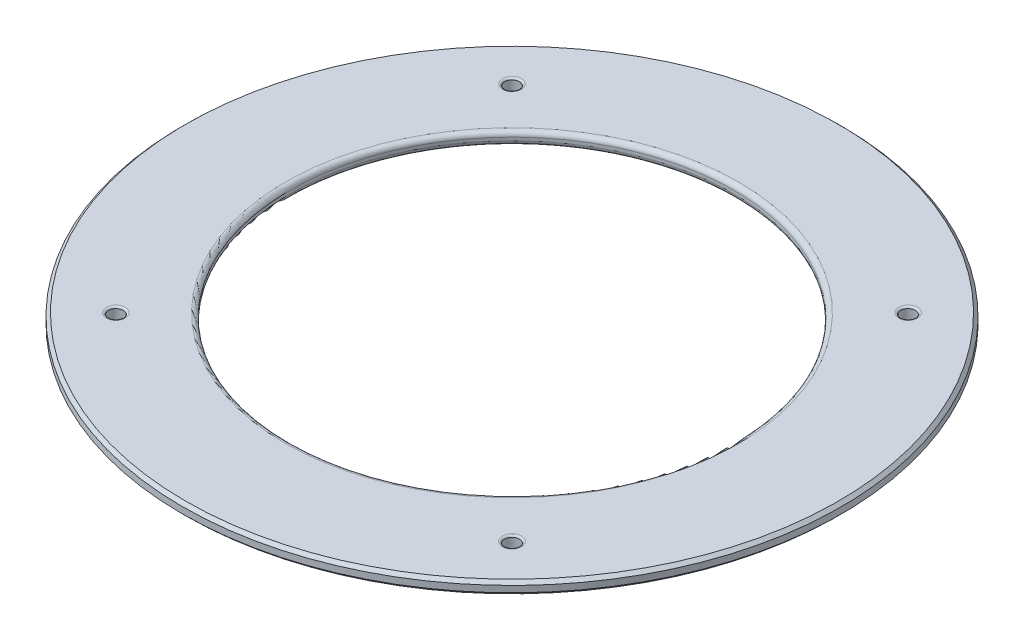
SolidWorks part; units mm, degrees
ref_plane "Front Plane" through (0, 0, 0) normal (0, 0, 1) x (1, 0, 0)
ref_plane "Top Plane" through (0, 0, 0) normal (0, 1, 0) x (1, 0, 0)
ref_plane "Right Plane" through (0, 0, 0) normal (1, 0, 0) x (0, 0, -1)
sketch "Sketch2" plane through (0, 0, 0) normal (0, 1, 0) x (1, 0, 0)
  circle A0 centre (0, 0) radius 104
  dimension "D1" = 208
extrude "Boss-Extrude3" add sketch "Sketch2" along normal blind 4
sketch "Sketch3" plane through (0, 4, 0) normal (0, 1, 0) x (1, 0, 0)
  line L1 (-62.5, -62.5) -> (62.5, -62.5)
  line L2 (-62.5, -62.5) -> (-62.5, 62.5)
  line L3 (-62.5, 62.5) -> (62.5, 62.5)
  line L4 (62.5, -62.5) -> (62.5, 62.5)
  line L5 (-62.5, -62.5) -> (62.5, 62.5) construction
  line L6 (-62.5, 62.5) -> (62.5, -62.5) construction
  point P0 (0, 0)
  dimension "D1" = 125
  dimension "D2" = 125
sketch "Sketch6" plane through (0, 4, 0) normal (0, 1, 0) x (1, 0, 0)
  point P0 (-62.5, 62.5)
  point P3 (62.5, 62.5)
  point P6 (62.5, -62.5)
  point P9 (-62.5, -62.5)
hole_wizard "Ø1.0mm Dowel Hole1" positions "Sketch6" profile "Sketch5" hole size "Ø1.0" standard "ISO" end condition through all
sketch "Sketch5" plane through (-62.5, 4, -62.5) normal (1, 0, 0) x (0, 0, 1)
  line L0 (0, 0) -> (0, 4)
  line L1 (0, 4) -> (2.3, 4)
  line L2 (2.3, 4) -> (2.3, 0)
  line L5 (2.3, 0) -> (0, 0)
  line L11 (0, -6.35) -> (0, 107.95) construction
  dimension "Thru Hole Dia." = 4.6
  dimension "Thru Hole Depth" = 4
sketch "Sketch7" plane through (0, 4, 0) normal (0, 1, 0) x (1, 0, 0)
  line L0 (-62.5, -62.5) -> (62.5, 62.5) construction
  line L1 (-70, -70) -> (70, -70)
  line L2 (-70, -70) -> (-70, 70)
  line L3 (-70, 70) -> (70, 70)
  line L4 (70, -70) -> (70, 70)
  line L5 (-70, -70) -> (70, 70) construction
  line L6 (-70, 70) -> (70, -70) construction
  circle A0 centre (0, 0) radius 70
  point P1 (0, 0)
  dimension "D1" = 140
extrude "Cut-Extrude1" cut sketch "Sketch7" against normal blind 4 contours A0
fillet "Fillet1" radius 1.5 2 edges at (0, 4, 70) (0, 0, 70)
sketch "Sketch8" plane through (0, 0, 0) normal (0, -1, 0) x (1, 0, 0)
  circle A0 centre (-62.5, -62.5) radius 2.85
  circle A1 centre (62.5, -62.5) radius 2.85
  circle A2 centre (62.5, 62.5) radius 2.85
  circle A3 centre (-62.5, 62.5) radius 2.85
  dimension "D1" = 5.7
  dimension "D2" = 5.7
  dimension "D3" = 5.7
  dimension "D4" = 5.7
extrude "Cut-Extrude2" cut sketch "Sketch8" against normal blind 3.5 contours A3
extrude "Cut-Extrude3" cut sketch "Sketch8<3>" against normal blind 3.5
sketch "Sketch8<3>" plane through (0, 0, 0) normal (0, -1, 0) x (1, 0, 0) same geometry as "Sketch8"
chamfer "Chamfer1" distance 1 angle 45 2 edges at (0, 0, 104) (0, 4, 104)
fillet "Fillet2" radius 0.7 1 edges at (-62.5, 4, -60.2)
fillet "Fillet3" radius 0.7 1 edges at (62.5, 4, -60.2)
fillet "Fillet4" radius 0.7 1 edges at (62.5, 4, 64.8)
fillet "Fillet5" radius 0.7 1 edges at (-62.5, 4, 64.8)
